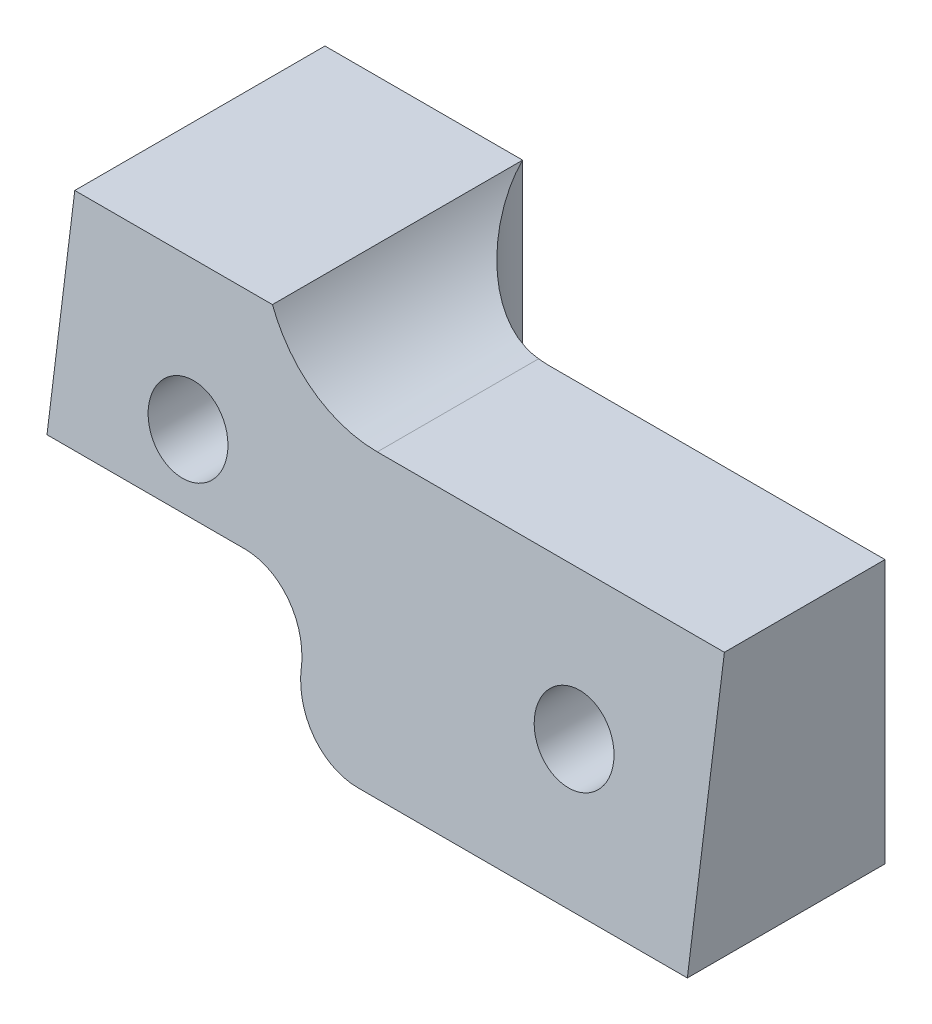
SolidWorks part; units mm, degrees
material "ABS"
ref_plane "Front Plane" through (0, 0, 0) normal (0, 0, 1) x (1, 0, 0)
ref_plane "Top Plane" through (0, 0, 0) normal (0, 1, 0) x (1, 0, 0)
ref_plane "Right Plane" through (0, 0, 0) normal (1, 0, 0) x (0, 0, -1)
sketch "Sketch1" plane through (0, 0, 0) normal (0, 0, 1) x (1, 0, 0)
  line L0 (23, 21) -> (18, 21)
  line L1 (18, 11) -> (3, 11)
  line L2 (18, 11) -> (18, 26)
  line L3 (18, 26) -> (3, 26)
  line L4 (3, 11) -> (3, 26)
  line L5 (23, 21) -> (53, 21)
  line L6 (23, 21) -> (23, 1)
  line L7 (23, 1) -> (53, 1)
  line L8 (53, 21) -> (53, 1)
  line L9 (18, 11) -> (23, 11)
  circle A0 centre (13, 16) radius 3
  circle A1 centre (43, 11) radius 3
  dimension "D9" = 6
  dimension "D1" = 15
  dimension "D2" = 15
  dimension "D3" = 10
  dimension "D4" = 10
  dimension "D5" = 20
  dimension "D6" = 30
  dimension "D7" = 5
  dimension "D8" = 30
  dimension "D10" = 10
  dimension "D11" = 10
extrude "Boss-Extrude1" add sketch "Sketch1" against normal blind 22.5 contours L4 L1 L2 L3 A0 region at (10.1407, 18.8593, 0)
extrude "Boss-Extrude2" add sketch "Sketch1<6>" against normal blind 15 contours L2 L9 L6 L0 | L8 L5 L6 L7 A1 region at (20.5, 16, 0) region at (37.7527, 11, 0)
sketch "Sketch1<6>" plane through (0, 0, 0) normal (0, 0, 1) x (1, 0, 0) same geometry as "Sketch1"
fillet "Fillet1" radius 10 2 edges
fillet "Fillet2" radius 5 2 edges at (23, 11, -8.082) (23, 1, -8.082)
sketch "Sketch2" plane through (53, 0, 0) normal (1, 0, 0) x (0, 0, -1)
  line L0 (0, 1) -> (3.5135, 26)
  line L1 (22.5, 26) -> (0, 26) construction
  line L2 (3.5135, 26) -> (0, 26)
  line L3 (0, 26) -> (0, 1)
  dimension "D1" = 8
extrude "Cut-Extrude1" cut sketch "Sketch2" against normal through all
